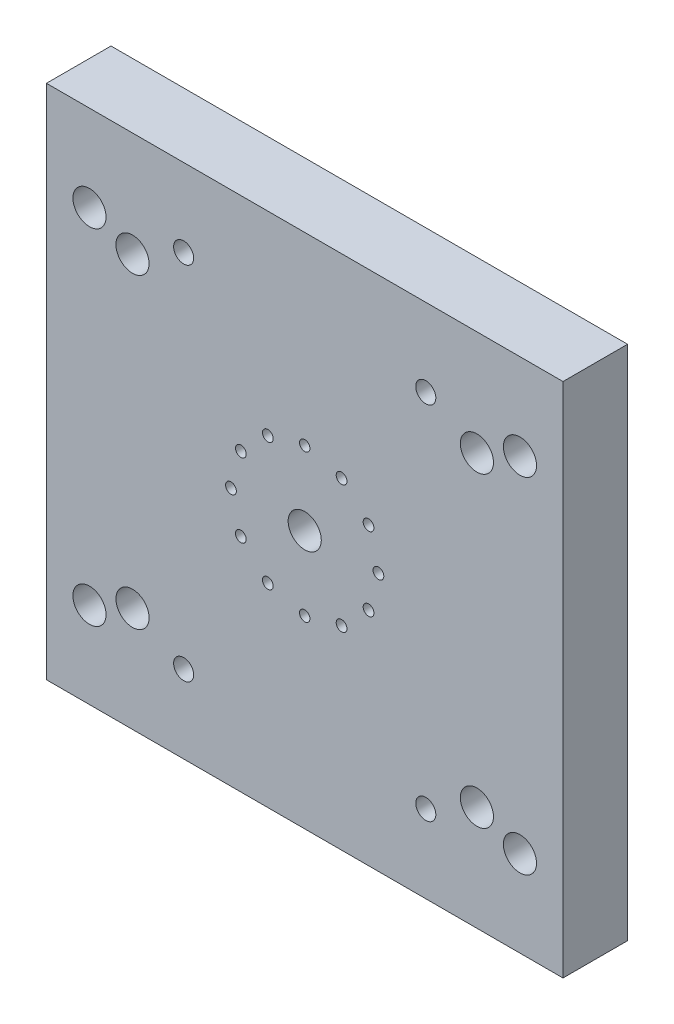
SolidWorks part; units mm, degrees
ref_plane "Front Plane" through (0, 0, 0) normal (0, 0, 1) x (1, 0, 0)
ref_plane "Top Plane" through (0, 0, 0) normal (0, 1, 0) x (1, 0, 0)
ref_plane "Right Plane" through (0, 0, 0) normal (1, 0, 0) x (0, 0, -1)
sketch "Sketch1" plane through (0, 0, 0) normal (0, 0, 1) x (1, 0, 0)
  line L1 (-152.4, 152.4) -> (152.4, 152.4)
  line L2 (-152.4, 152.4) -> (-152.4, -152.4)
  line L3 (-152.4, -152.4) -> (152.4, -152.4)
  line L4 (152.4, 152.4) -> (152.4, -152.4)
  line L5 (-152.4, 152.4) -> (152.4, -152.4) construction
  line L6 (-152.4, -152.4) -> (152.4, 152.4) construction
  point P0 (0, 0)
  dimension "D1" = 304.8
  dimension "D2" = 304.8
extrude "Boss-Extrude1" add sketch "Sketch1" along normal blind 38.1
sketch "Sketch2" plane through (0, 0, 38.1) normal (0, 0, 1) x (1, 0, 0)
  line L0 (-152.4, 0) -> (152.4, 0) construction
  line L5 (-152.4, 152.4) -> (-152.4, -152.4) construction
  line L6 (152.4, -152.4) -> (152.4, 152.4) construction
  line L7 (-152.4, -101.6) -> (152.4, -101.6) construction
  line L8 (-152.4, 101.6) -> (152.4, 101.6) construction
  line L9 (0, 101.6) -> (0, -101.6) construction
  line L10 (127, 101.6) -> (127, -101.6) construction
  line L11 (-127, 101.6) -> (-127, -101.6) construction
  circle A0 centre (-127, 101.6) radius 6.5151
  circle A1 centre (127, 101.6) radius 6.5151
  circle A2 centre (127, -101.6) radius 6.5151
  circle A3 centre (-127, -101.6) radius 6.5151
  circle A4 centre (0, 0) radius 6.5151
  dimension "D5" = 13.0302
  dimension "D1" = 101.6
  dimension "D2" = 101.6
  dimension "D3" = 127
  dimension "D4" = 127
extrude "HAAS T-Slot Holes" cut sketch "Sketch2" against normal through all
sketch "Sketch3" plane through (0, 0, 38.1) normal (0, 0, 1) x (1, 0, 0)
  circle A0 centre (-127, 101.6) radius 9.779
  circle A1 centre (127, 101.6) radius 9.779
  circle A2 centre (0, 0) radius 9.779
  circle A3 centre (127, -101.6) radius 9.779
  circle A4 centre (-127, -101.6) radius 9.779
  dimension "D1" = 19.558
extrude "HAAS Counter Bores" cut sketch "Sketch3" against normal offset from surface (22.225 mm away) 15.875 contours A0 | A1 | A2 | A3 | A4 up to face at (6.5151, 0, 0)
sketch "Sketch4" plane through (0, 0, 38.1) normal (0, 0, 1) x (1, 0, 0)
  line L0 (-127, 90.4875) -> (127, 90.4875) construction
  line L1 (-127, 30.1625) -> (127, 30.1625) construction
  line L2 (-127, 30.1625) -> (-127, -30.1625) construction
  line L3 (-127, -30.1625) -> (127, -30.1625) construction
  line L4 (127, 30.1625) -> (127, -30.1625) construction
  line L5 (-127, 30.1625) -> (127, -30.1625) construction
  line L6 (-127, -30.1625) -> (127, 30.1625) construction
  line L7 (-127, -90.4875) -> (127, -90.4875) construction
  line L8 (-101.6, 90.4875) -> (-101.6, 84.1375) construction
  line L9 (-101.6, -90.4875) -> (-101.6, -84.1375) construction
  line L10 (101.6, -90.4875) -> (101.6, -84.1375) construction
  line L11 (101.6, 90.4875) -> (101.6, 84.1375) construction
  circle A0 centre (-101.6, 90.4875) radius 6.5151
  circle A1 centre (101.6, 90.4875) radius 6.5151
  circle A2 centre (-101.6, -90.4875) radius 6.5151
  circle A3 centre (101.6, -90.4875) radius 6.5151
  point P0 (0, 0)
  dimension "D9" = 13.0302
  dimension "D1" = 60.325
  dimension "D2" = 254
  dimension "D5" = 203.2
  dimension "D6" = 25.4
  dimension "D7" = 203.2
  dimension "D8" = 6.35
  dimension "D3" = 60.325
  dimension "D4" = 60.325
extrude "Tormach T-Slot Holes" cut sketch "Sketch4" against normal through all
sketch "Sketch5" plane through (0, 0, 38.1) normal (0, 0, 1) x (1, 0, 0)
  circle A0 centre (-101.6, 90.4875) radius 9.779
  circle A1 centre (101.6, 90.4875) radius 9.779
  circle A2 centre (101.6, -90.4875) radius 9.779
  circle A3 centre (-101.6, -90.4875) radius 9.779
  dimension "D1" = 19.558
extrude "Tormach Counter bores" cut sketch "Sketch5" against normal up to surface (22.225 mm away) up to face at (-117.221, 101.6, 15.875)
sketch "Sketch6" plane through (0, 0, 38.1) normal (0, 0, 1) x (1, 0, 0)
  circle A0 centre (0, 0) radius 43.5 construction
  circle A1 centre (0, 43.5) radius 3.0734
  circle A2 centre (0, -43.5) radius 3.0734
  dimension "D1" = 87.0001
  dimension "D2" = 6.1468
extrude "Sprocket Locating Holes" cut sketch "Sketch6" against normal blind 6.35
sketch "Sketch7" plane through (0, 0, 38.1) normal (0, 0, 1) x (1, 0, 0)
  circle A0 centre (0, 0) radius 43.5 construction
  circle A2 centre (43.5, 0) radius 3.175
  circle A4 centre (37.6721, -21.75) radius 3.175
  circle A5 centre (21.75, -37.6721) radius 3.175
  circle A6 centre (0, -43.5) radius 3.175 [skipped]
  circle A7 centre (-21.75, -37.6721) radius 3.175
  circle A8 centre (-37.6721, -21.75) radius 3.175
  circle A9 centre (-43.5, 0) radius 3.175
  circle A10 centre (-37.6721, 21.75) radius 3.175
  circle A11 centre (-21.75, 37.6721) radius 3.175
  circle A12 centre (0, 43.5) radius 3.175 [skipped]
  circle A13 centre (21.75, 37.6721) radius 3.175
  circle A14 centre (37.6721, 21.75) radius 3.175
  point P31 (0, 0)
  dimension "D1" = 87.0001
  dimension "D2" = 6.35
  dimension "D3" = 12
extrude "Sprocket Mounting clearance holes" cut sketch "Sketch7" against normal blind 9.525
sketch "Sketch8" plane through (0, 0, 38.1) normal (0, 0, 1) x (1, 0, 0)
  line L1 (-71.4375, 106.4641) -> (71.4375, 106.4641) construction
  line L2 (-71.4375, 106.4641) -> (-71.4375, -106.4641) construction
  line L3 (-71.4375, -106.4641) -> (71.4375, -106.4641) construction
  line L4 (71.4375, 106.4641) -> (71.4375, -106.4641) construction
  line L5 (-71.4375, 106.4641) -> (71.4375, -106.4641) construction
  line L6 (-71.4375, -106.4641) -> (71.4375, 106.4641) construction
  circle A0 centre (-71.4375, 106.4641) radius 5.9182
  circle A1 centre (71.4375, 106.4641) radius 5.9182
  circle A2 centre (71.4375, -106.4641) radius 5.9182
  circle A3 centre (-71.4375, -106.4641) radius 5.9182
  point P0 (0, 0)
  dimension "D3" = 11.8364
  dimension "D1" = 142.875
  dimension "D2" = 212.9282
extrude "1/2-13 Tapped Holes" cut sketch "Sketch8" against normal blind 19.05
